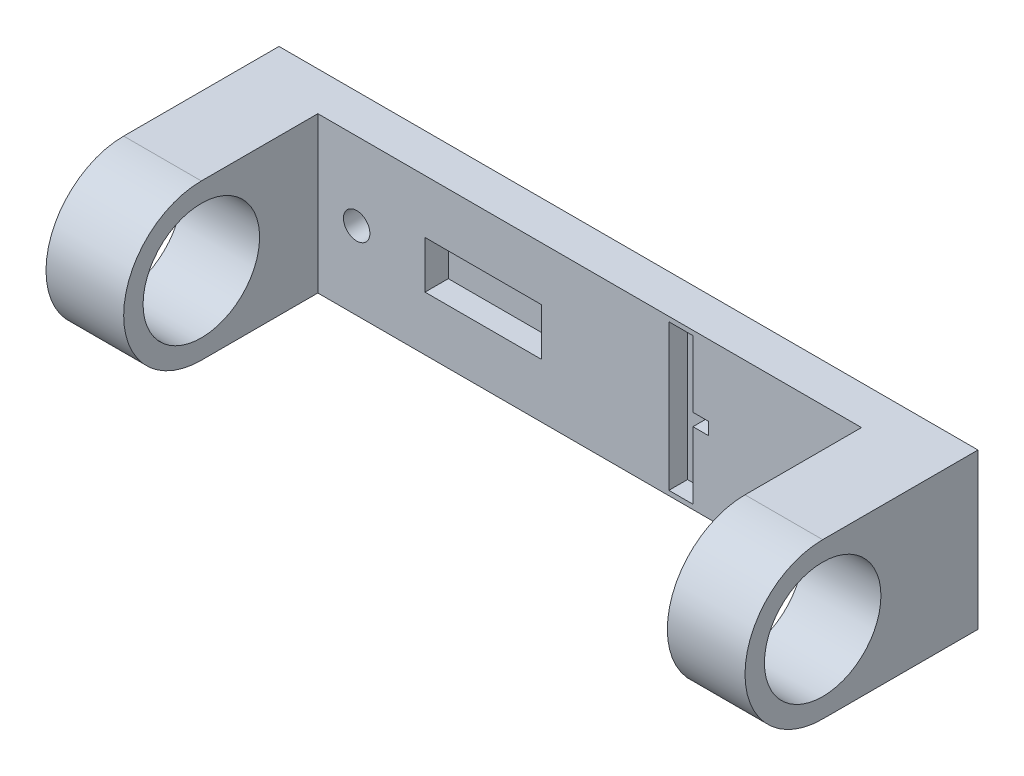
SolidWorks part; units mm, degrees
ref_plane "Plan de face" through (0, 0, 0) normal (0, 0, 1) x (1, 0, 0)
ref_plane "Plan de dessus" through (0, 0, 0) normal (0, 1, 0) x (1, 0, 0)
ref_plane "Plan de droite" through (0, 0, 0) normal (1, 0, 0) x (0, 0, -1)
sketch "Esquisse1" plane through (0, 0, 0) normal (0, 0, 1) x (1, 0, 0)
  line L1 (0, 0) -> (90, 0)
  line L2 (0, 0) -> (0, 20)
  line L3 (0, 20) -> (90, 20)
  line L4 (90, 0) -> (90, 20)
  dimension "D1" = 90
  dimension "D2" = 20
extrude "Boss.-Extru.1" add sketch "Esquisse1" along normal blind 5
sketch "Esquisse2" plane through (0, 0, 5) normal (0, 0, 1) x (1, 0, 0)
  line L0 (90, 20) -> (0, 20) construction
  line L1 (0, 0) -> (10, 0)
  line L2 (0, 0) -> (0, 20)
  line L3 (0, 20) -> (10, 20)
  line L4 (10, 0) -> (10, 20)
  dimension "D1" = 10
extrude "Boss.-Extru.2" add sketch "Esquisse2" along normal blind 30
sketch "Esquisse3" plane through (0, 0, 0) normal (-1, 0, 0) x (0, 0, 1)
  line L0 (0, 20) -> (0, 0) construction
  line L1 (35, 20) -> (0, 20) construction
  line L2 (35, 20) -> (35, 0) construction
  line L3 (35, 0) -> (0, 0) construction
  line L4 (35, 20) -> (20, 20)
  line L5 (35, 20) -> (35, 0)
  line L6 (35, 0) -> (20, 0)
  circle A0 centre (20, 10) radius 7.5
  arc A1 (20, 0) -> (20, 20) centre (20, 10) ccw
  dimension "D2" = 15
  dimension "D4" = 20
  dimension "D1" = 20
  dimension "D3" = 10
extrude "Enlèv. mat.-Extru.1" cut sketch "Esquisse3" against normal up to surface (10 mm away) up to face at (10, 10, 20)
ref_plane "Plan1" through (45, 0, 0) normal (1, 0, 0) x (0, 0, -1)
mirror "Symétrie1" about plane through (45, 0, 0) normal (1, 0, 0) of "Enlèv. mat.-Extru.1", "Boss.-Extru.2"
sketch "Esquisse5" plane through (0, 0, 5) normal (0, 0, 1) x (1, 0, 0)
  line L0 (80, 20) -> (10, 20) construction
  line L1 (55.2, 19.4) -> (58.3, 19.4)
  line L2 (55.2, 19.4) -> (55.2, 0.6)
  line L3 (55.2, 0.6) -> (58.3, 0.6)
  line L4 (58.3, 19.4) -> (58.3, 10.85)
  line L5 (80, 0) -> (80, 20) construction
  line L6 (58.3, 10.85) -> (60.3, 10.85)
  line L7 (60.3, 10.85) -> (60.3, 9.25)
  line L8 (60.3, 9.25) -> (58.3, 9.25)
  line L9 (58.3, 9.25) -> (58.3, 0.6)
  dimension "D1" = 18.8
  dimension "D2" = 3.1
  dimension "D3" = 0.6
  dimension "D4" = 21.7
  dimension "D5" = 8.65
  dimension "D6" = 1.6
  dimension "D7" = 2
extrude "Enlèv. mat.-Extru.2" cut sketch "Esquisse5" against normal offset from surface (2.4 mm away) 2.6 up to face at (45, 10, 0)
sketch "Esquisse6" plane through (0, 0, 5) normal (0, 0, 1) x (1, 0, 0)
  line L0 (80, 20) -> (10, 20) construction
  line L1 (10, 0) -> (10, 20) construction
  line L2 (80, 20) -> (80, 0) construction
  circle A0 centre (25, 10) radius 1.5 construction
  circle A1 centre (68, 10) radius 1.5
  dimension "D1" = 3
  dimension "D4" = 3
  dimension "D2" = 10
  dimension "D3" = 15
  dimension "D5" = 10
  dimension "D6" = 12
extrude "Enlèv. mat.-Extru.3" [suppressed] cut sketch "Esquisse6" against normal up to surface (5 mm away) up to face at (45, 10, 0)
sketch "Esquisse10" plane through (0, 0, 5) normal (0, 0, 1) x (1, 0, 0)
  line L0 (55.2, 19.4) -> (55.2, 0.6) construction
  line L1 (23.8, 13.1) -> (38.8, 13.1)
  line L2 (23.8, 13.1) -> (23.8, 7)
  line L3 (23.8, 7) -> (38.8, 7)
  line L4 (38.8, 13.1) -> (38.8, 7)
  line L5 (60.3, 10.05) -> (75.5405, 10.05) construction
  line L6 (60.3, 9.25) -> (60.3, 10.85) construction
  point P10 (23.8, 10.05)
  dimension "D1" = 16.4
  dimension "D2" = 15
  dimension "D3" = 6.1
extrude "Enlèv. mat.-Extru.4" cut sketch "Esquisse10" against normal offset from surface (3 mm away) 2 up to face at (45, 10, 0)
sketch "Esquisse11" plane through (0, 0, 5) normal (0, 0, 1) x (1, 0, 0)
  line L0 (0, 10) -> (91.8744, 10) construction
  line L1 (90, 0) -> (90, 20) construction
  line L4 (0, 20) -> (0, 0)
  line L5 (90, 20) -> (0, 20)
  line L6 (90, 0) -> (90, 20)
  line L7 (0, 0) -> (90, 0)
  line L8 (0, 20) -> (0, 0) construction
  line L9 (90, 20) -> (0, 20) construction
  line L10 (90, 0) -> (90, 20) construction
  line L11 (0, 0) -> (90, 0) construction
  circle A0 centre (15, 10) radius 1
  circle A1 centre (75, 10) radius 1
  dimension "D2" = 2
  dimension "D3" = 2
  dimension "D4" = 15
  dimension "D5" = 15
  dimension "D1" = 0
extrude "Enlèv. mat.-Extru.5" cut sketch "Esquisse11" against normal blind 10
hole_wizard "Dégagement M31" positions "Esquisse12" profile "Esquisse13" hole size "M3" standard "ISO" end condition through all
sketch "Esquisse12" plane through (0, 0, 5) normal (0, 0, 1) x (1, 0, 0)
  point P0 (15, 10)
  point P3 (75, 10)
sketch "Esquisse13" plane through (15, 10, 5) normal (1, 0, 0) x (0, -1, 0)
  line L0 (0, 0) -> (0, 5)
  line L1 (0, 5) -> (1.7, 5)
  line L2 (1.7, 5) -> (1.7, 0)
  line L5 (1.7, 0) -> (0, 0)
  line L11 (0, -6.35) -> (0, 107.95) construction
  dimension "Diamètre du perçage jusqu'au prochain" = 3.4
  dimension "Profondeur du perçage jusqu'au prochain" = 5
equation "\"D3@Esquisse5\"=(20-\"D1@Esquisse5\")/2"
